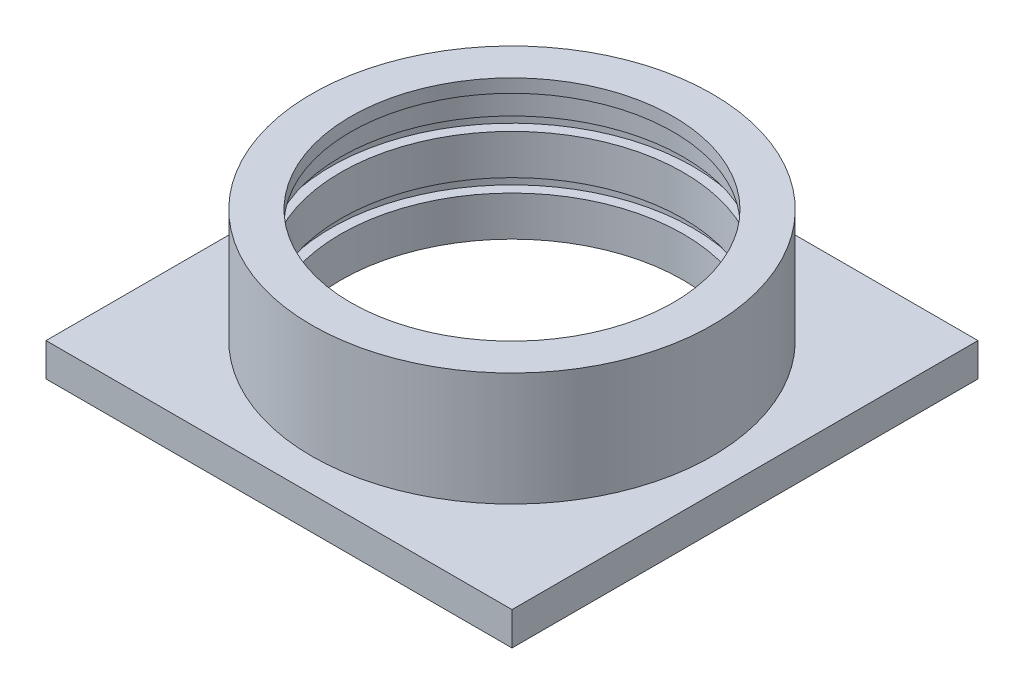
SolidWorks part; units mm, degrees
ref_plane "Front Plane" through (0, 0, 0) normal (0, 0, 1) x (1, 0, 0)
ref_plane "Top Plane" through (0, 0, 0) normal (0, 1, 0) x (1, 0, 0)
ref_plane "Right Plane" through (0, 0, 0) normal (1, 0, 0) x (0, 0, -1)
sketch "Sketch1" plane through (0, 0, 0) normal (0, 1, 0) x (1, 0, 0)
  line L1 (-34.9, 34.9) -> (34.9, 34.9)
  line L2 (-34.9, 34.9) -> (-34.9, -34.9)
  line L3 (-34.9, -34.9) -> (34.9, -34.9)
  line L4 (34.9, 34.9) -> (34.9, -34.9)
  line L5 (-34.9, 34.9) -> (34.9, -34.9) construction
  line L6 (-34.9, -34.9) -> (34.9, 34.9) construction
  point P0 (0, 0)
  dimension "D1" = 69.8
  dimension "D2" = 69.8
extrude "Boss-Extrude1" add sketch "Sketch1" against normal blind 4.98
sketch "Sketch2" plane through (0, 0, 0) normal (0, 1, 0) x (1, 0, 0)
  circle A0 centre (0, 0) radius 30
  dimension "D1" = 60
extrude "Boss-Extrude2" add sketch "Sketch2" along normal blind 17
sketch "Sketch3" plane through (0, -4.98, 0) normal (0, -1, 0) x (1, 0, 0)
  circle A0 centre (0, 0) radius 25.65
  dimension "D1" = 51.3
extrude "Cut-Extrude1" cut sketch "Sketch3" against normal blind 19.98
sketch "Sketch4" plane through (0, 17, 0) normal (0, 1, 0) x (1, 0, 0)
  circle A0 centre (0, 0) radius 24.15
  dimension "D1" = 48.3
extrude "Cut-Extrude3" cut sketch "Sketch4" against normal blind 2
sketch "Sketch5" plane through (0, 17, 0) normal (0, 1, 0) x (1, 0, 0)
  circle A0 centre (0, 0) radius 27.15
  dimension "D1" = 54.3
extrude "Cut-Extrude4" cut sketch "Sketch5" against normal blind 2 from offset 6 offset against normal yes
extrude "Cut-Extrude5" cut sketch "Sketch5<2>" against normal blind 2 from offset 14 offset against normal yes
sketch "Sketch5<2>" plane through (0, 17, 0) normal (0, 1, 0) x (1, 0, 0) same geometry as "Sketch5"
sketch "Sketch6" plane through (0, 0, 0) normal (1, 0, 0) x (0, 0, -1)
  circle A0 centre (0, 7.6122) radius 3.3422
